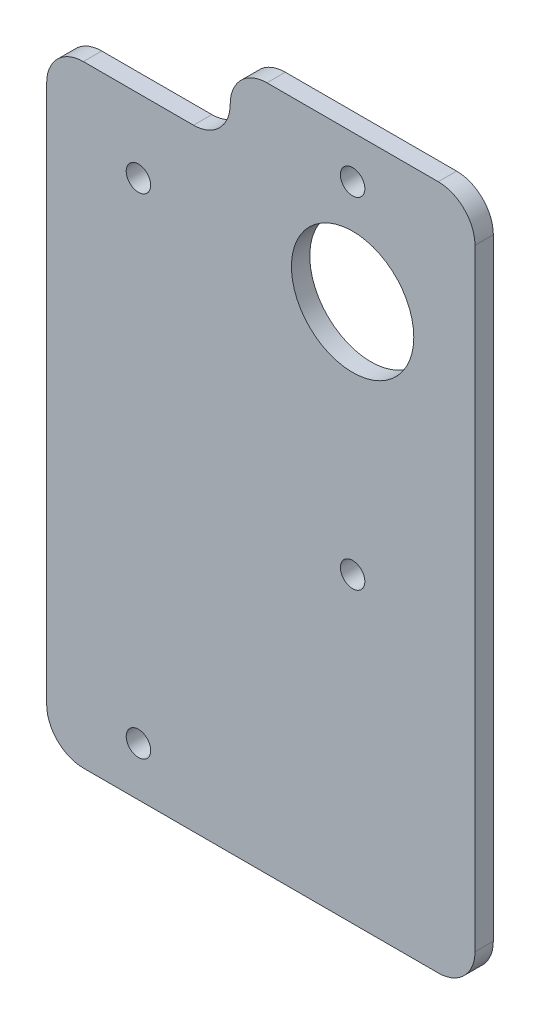
SolidWorks part; units mm, degrees
ref_plane "前视基准面" through (0, 0, 0) normal (0, 0, 1) x (1, 0, 0)
ref_plane "上视基准面" through (0, 0, 0) normal (0, 1, 0) x (1, 0, 0)
ref_plane "右视基准面" through (0, 0, 0) normal (1, 0, 0) x (0, 0, -1)
sketch "草图1" plane through (0, 0, 0) normal (0, 0, 1) x (1, 0, 0)
  line L1 (7.5, 22.5) -> (-7.5, 22.5)
  line L3 (7.5, -27.5) -> (-7.5, -27.5)
  line L4 (-7.5, 22.5) -> (-7.5, -27.5)
  line L5 (0, -27.5) -> (0, 22.5) construction
  line L9 (27.5, 2.5) -> (27.5, 14.5)
  line L10 (27.5, 22.5) -> (27.5, 14.5)
  line L11 (17.5, 16.5) -> (0, 16.5) construction
  line L14 (7.5, -27.5) -> (27.5, -27.5)
  line L15 (27.5, -27.5) -> (27.5, 2.5)
  line L18 (27.5, 22.5) -> (27.5, 28.5)
  line L19 (27.5, 28.5) -> (7.5, 28.5)
  line L20 (7.5, 22.5) -> (7.5, 28.5)
  line L21 (27.5, 22.5) -> (7.5, 28.5) construction
  line L22 (27.5, 28.5) -> (7.5, 22.5) construction
  circle A0 centre (0, -23.5) radius 1
  circle A1 centre (0, 16.5) radius 1
  circle A4 centre (17.5, 16.5) radius 5
  point P0 (0, 0)
  point P14 (17.5, 25.5)
  dimension "D3" = 6
  dimension "D5" = 20
  dimension "D7" = 10
  dimension "D8" = 2
  dimension "D9" = 2
  dimension "D1" = 15
  dimension "D2" = 50
  dimension "D4" = 4
  dimension "D6" = 6
  dimension "D10" = 20
extrude "凸台-拉伸1" add sketch "草图1" along normal blind 1.5
sketch "草图3" plane through (0, 0, 1.5) normal (0, 0, 1) x (1, 0, 0)
  circle A0 centre (17.5, -2.8) radius 1
  circle A1 centre (17.5, 25) radius 1
extrude "切除-拉伸1" cut sketch "草图3" against normal blind 10
fillet "圆角1" radius 3 6 edges at (7.5, 22.5, 0.75) (7.5, 28.5, 0.75) (-7.5, 22.5, 0.75) (27.5, 28.5, 0.75) (-7.5, -27.5, 0.75) (27.5, -27.5, 0.75)
